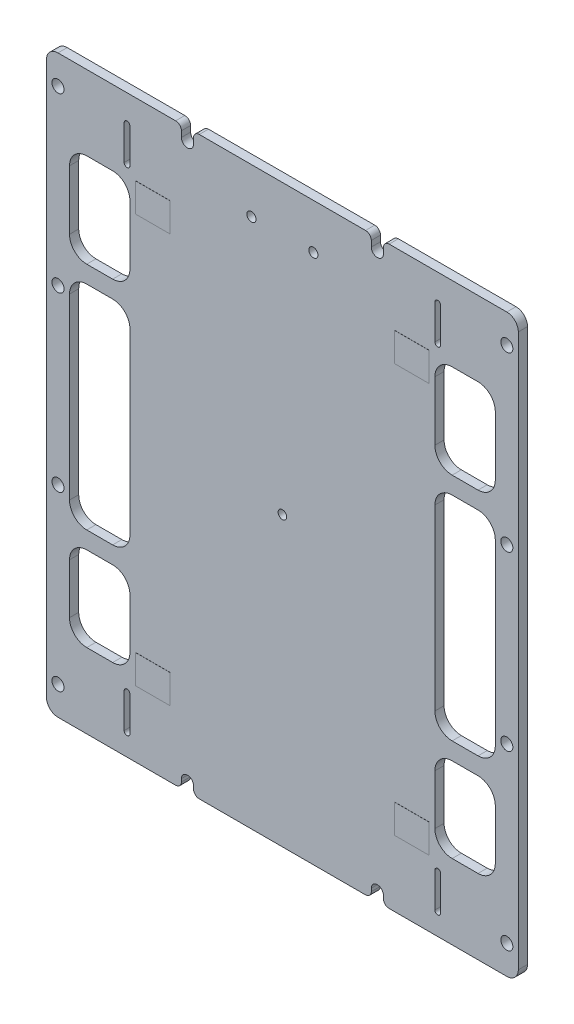
SolidWorks part; units mm, degrees
material "FR4_stuffedProtoboard"
ref_plane "Front Plane" through (0, 0, 0) normal (0, 0, 1) x (1, 0, 0)
ref_plane "Top Plane" through (0, 0, 0) normal (0, 1, 0) x (1, 0, 0)
ref_plane "Right Plane" through (0, 0, 0) normal (1, 0, 0) x (0, 0, -1)
sketch "Sketch1" plane through (0, 0, 0) normal (0, 0, 1) x (1, 0, 0)
  line L1 (-39, -50) -> (39, -50)
  line L2 (-41, -48) -> (-41, 48)
  line L3 (-39, 50) -> (39, 50)
  line L4 (41, -48) -> (41, 48)
  line L5 (-41, -50) -> (41, 50) construction
  line L6 (-41, 50) -> (41, -50) construction
  arc A0 (-39, -50) -> (-41, -48) centre (-39, -48) cw
  arc A1 (39, -50) -> (41, -48) centre (39, -48) ccw
  arc A2 (39, 50) -> (41, 48) centre (39, 48) cw
  arc A3 (-41, 48) -> (-39, 50) centre (-39, 48) cw
  point P0 (0, 0)
  dimension "D3" = 2
  dimension "D1" = 100
  dimension "D2" = 82
extrude "boardOutline" add sketch "Sketch1" along normal blind 1.6
sketch "Sketch2" plane through (0, 0, 1.6) normal (0, 0, 1) x (1, 0, 0)
  line L0 (39, 50) -> (-39, 50) construction
  line L1 (-41, 48) -> (-41, -48) construction
  line L2 (-5.385, 42.15) -> (5.385, 42.15) construction
  line L3 (-37.5, 44.2) -> (-37.5, 4.2) construction
  line L4 (0, 42.15) -> (0, 50) construction
  circle A0 centre (0, 0) radius 0.75
  circle A1 centre (-37.5, 44.2) radius 1.05 construction
  circle A2 centre (37.5, 44.2) radius 1.05 construction
  circle A3 centre (37.5, 4.2) radius 1.05 construction
  circle A4 centre (37.5, -35.8) radius 1.05 construction
  circle A5 centre (-37.5, 4.2) radius 1.05 construction
  circle A6 centre (-37.5, -35.8) radius 1.05 construction
  circle A7 centre (-5.385, 42.15) radius 0.8
  circle A8 centre (5.385, 42.15) radius 0.8
  point P27 (0, 0)
  dimension "D1" = 1.5
  dimension "D2" = 2.1
  dimension "D9" = 10.77
  dimension "D7" = 1.6
  dimension "D11" = 7.85
  dimension "D3" = 5.8
  dimension "D4" = 3.5
  dimension "D8" = 40
  dimension "D10" = 37.5
  dimension "D5" = 2
  dimension "D6" = 3
extrude "componentHoles" cut sketch "Sketch2" against normal through all
sketch "Sketch4" plane through (0, 0, 1.6) normal (0, 0, 1) x (1, 0, 0)
  line L0 (-27, 39.25) -> (-27, 45.25) construction
  line L1 (-27.5, 39.25) -> (-27.5, 45.25)
  line L2 (-26.5, 39.25) -> (-26.5, 45.25)
  line L3 (39, 50) -> (-39, 50) construction
  line L4 (-41, 48) -> (-41, -48) construction
  line L5 (27, 39.25) -> (27, 45.25) construction
  line L6 (26.5, 39.25) -> (26.5, 45.25)
  line L7 (27.5, 39.25) -> (27.5, 45.25)
  line L8 (27, -46.25) -> (27, -40.25) construction
  line L9 (26.5, -46.25) -> (26.5, -40.25)
  line L10 (27.5, -46.25) -> (27.5, -40.25)
  line L11 (-27, -46.25) -> (-27, -40.25) construction
  line L12 (-27.5, -46.25) -> (-27.5, -40.25)
  line L13 (-26.5, -46.25) -> (-26.5, -40.25)
  line L14 (-27, 39.25) -> (27, 39.25) construction
  line L15 (0, 39.25) -> (0, 50) construction
  arc A0 (-27.5, 39.25) -> (-26.5, 39.25) centre (-27, 39.25) ccw
  arc A1 (-26.5, 45.25) -> (-27.5, 45.25) centre (-27, 45.25) ccw
  arc A2 (26.5, 39.25) -> (27.5, 39.25) centre (27, 39.25) ccw
  arc A3 (27.5, 45.25) -> (26.5, 45.25) centre (27, 45.25) ccw
  arc A4 (26.5, -46.25) -> (27.5, -46.25) centre (27, -46.25) ccw
  arc A5 (27.5, -40.25) -> (26.5, -40.25) centre (27, -40.25) ccw
  arc A6 (-27.5, -46.25) -> (-26.5, -46.25) centre (-27, -46.25) ccw
  arc A7 (-26.5, -40.25) -> (-27.5, -40.25) centre (-27, -40.25) ccw
  point P2 (-27, 42.25)
  point P16 (27, 42.25)
  point P23 (27, -43.25)
  point P30 (-27, -43.25)
  dimension "D1" = 4.75
  dimension "D2" = 13.5
  dimension "D3" = 1
  dimension "D4" = 6
  dimension "D7" = 54
  dimension "D9" = 79.5
  dimension "D5" = 2
  dimension "D6" = 2
extrude "solarCellContactHoles" cut sketch "Sketch4" against normal blind 1.6
sketch "Sketch3" plane through (0, 0, 1.6) normal (0, 0, 1) x (1, 0, 0)
  line L1 (-34, 37) -> (-29.5, 37)
  line L2 (-37, 34) -> (-37, 23.7)
  line L3 (-34, 20.7) -> (-29.5, 20.7)
  line L4 (-26.5, 34) -> (-26.5, 23.7)
  line L5 (-41, 48) -> (-41, -48) construction
  line L6 (-29.5, -22.3) -> (-34, -22.3)
  line L9 (0, 50) -> (0, -50) construction
  line L10 (39, 50) -> (-39, 50) construction
  line L11 (-39, -50) -> (39, -50) construction
  line L12 (-26.5, -25.3) -> (-26.5, -34)
  line L13 (-29.5, -37) -> (-34, -37)
  line L14 (-37, -25.3) -> (-37, -34)
  line L19 (-29.5, -19.3) -> (-34, -19.3)
  line L25 (-26.5, -16.3) -> (-26.5, 14.7)
  line L26 (-29.5, 17.7) -> (-34, 17.7)
  line L27 (-37, -16.3) -> (-37, 14.7)
  arc A0 (-37, 23.7) -> (-34, 20.7) centre (-34, 23.7) ccw
  arc A1 (-29.5, 20.7) -> (-26.5, 23.7) centre (-29.5, 23.7) ccw
  arc A2 (-29.5, 37) -> (-26.5, 34) centre (-29.5, 34) cw
  arc A3 (-34, 37) -> (-37, 34) centre (-34, 34) ccw
  arc A4 (-29.5, -19.3) -> (-26.5, -16.3) centre (-29.5, -16.3) ccw
  arc A5 (-26.5, -34) -> (-29.5, -37) centre (-29.5, -34) cw
  arc A6 (-34, -37) -> (-37, -34) centre (-34, -34) cw
  arc A7 (-34, -22.3) -> (-37, -25.3) centre (-34, -25.3) ccw
  arc A8 (-29.5, -22.3) -> (-26.5, -25.3) centre (-29.5, -25.3) cw
  arc A17 (-34, -19.3) -> (-37, -16.3) centre (-34, -16.3) cw
  arc A18 (-34, 17.7) -> (-37, 14.7) centre (-34, 14.7) ccw
  arc A19 (-26.5, 14.7) -> (-29.5, 17.7) centre (-29.5, 14.7) ccw
  point P12 (-26.5, 20.7)
  point P15 (-26.5, 37)
  point P18 (-37, 37)
  dimension "D5" = 3
  dimension "D10" = 13
  dimension "D7" = 3
  dimension "D11" = 3
  dimension "D1" = 10.5
  dimension "D2" = 29.3
  dimension "D3" = 13
  dimension "D4" = 4
  dimension "D8" = 3
  dimension "D9" = 3
  dimension "D6" = 37
extrude "windows_1side" cut sketch "Sketch3" against normal through all
sketch "Sketch5" plane through (0, 0, 1.6) normal (0, 0, 1) x (1, 0, 0)
  line L0 (-41, 48) -> (-41, -48) construction
  line L1 (-25.5, 37.5) -> (-19.5, 37.5)
  line L2 (-25.5, 37.5) -> (-25.5, 32.5)
  line L3 (-25.5, 32.5) -> (-19.5, 32.5)
  line L4 (-19.5, 37.5) -> (-19.5, 32.5)
  line L5 (0, 37.5) -> (0, 50) construction
  line L6 (19.5, 37.5) -> (19.5, 32.5)
  line L7 (25.5, 37.5) -> (25.5, 32.5)
  line L8 (19.5, 32.5) -> (25.5, 32.5)
  line L9 (19.5, 37.5) -> (25.5, 37.5)
  line L10 (19.5, -33.5) -> (19.5, -38.5)
  line L11 (25.5, -33.5) -> (25.5, -38.5)
  line L12 (19.5, -38.5) -> (25.5, -38.5)
  line L13 (19.5, -33.5) -> (25.5, -33.5)
  line L14 (-25.5, -33.5) -> (-25.5, -38.5)
  line L15 (-19.5, -33.5) -> (-19.5, -38.5)
  line L16 (-25.5, -38.5) -> (-19.5, -38.5)
  line L17 (-25.5, -33.5) -> (-19.5, -33.5)
  line L18 (-19.5, 37.5) -> (19.5, 37.5) construction
  line L19 (-25.5, 37.5) -> (-25.5, -33.5) construction
  line L20 (39, 50) -> (-39, 50) construction
  arc A0 (-27.5, 39.25) -> (-26.5, 39.25) centre (-27, 39.25) ccw construction
  point P9 (0, 0)
  dimension "D1" = 5
  dimension "D2" = 6
  dimension "D3" = 15.5
  dimension "D4" = 1.75
  dimension "D7" = 45
  dimension "D8" = 71
  dimension "D5" = 2
  dimension "D6" = 2
extrude "contactPads" add sketch "Sketch5" along normal blind 0.02
hole_wizard "M2 Clearance Hole1" positions "Sketch6" profile "Sketch7" hole size "M2" standard "ANSI Metric" end condition through all
sketch "Sketch6" plane through (0, 0, 0) normal (0, 0, -1) x (-1, 0, 0)
  line L5 (39, -50) -> (39, -45) construction
  line L6 (39, -50) -> (-39, -50) construction
  line L7 (39, -45) -> (39, -15) construction
  line L8 (39, -15) -> (39, 15) construction
  line L9 (39, 15) -> (39, 45) construction
  line L10 (39, 45) -> (39, 50) construction
  line L11 (-39, 50) -> (39, 50) construction
  line L15 (37, -27.0602) -> (41, -27.0602) construction
  line L16 (37, -25.3) -> (37, -34) construction
  line L17 (41, 48) -> (41, -48) construction
  point P0 (39, 45)
  point P27 (39, -15)
  point P36 (39, -45)
  point P38 (39, 15)
  point P73 (39, -27.0602)
  dimension "D2" = 5
sketch "Sketch7" plane through (-39, 45, 0) normal (1, 0, 0) x (0, 1, 0)
  line L0 (0, 0) -> (0, 1.62)
  line L1 (0, 1.62) -> (1.05, 1.62)
  line L2 (1.05, 1.62) -> (1.05, 0)
  line L5 (1.05, 0) -> (0, 0)
  line L11 (0, -6.35) -> (0, 107.95) construction
  dimension "Thru Hole Dia." = 2.1
  dimension "Thru Hole Depth" = 1.62
sketch "Sketch10" plane through (0, 0, 0) normal (0, 0, -1) x (-1, 0, 0)
  line L0 (16.5, 48) -> (16.5, 55.0732) construction
  line L1 (15.45, 48) -> (15.45, 55.0732)
  line L2 (17.55, 48) -> (17.55, 55.0732)
  line L3 (16.5, -48.5) -> (16.5, -55.5732) construction
  line L4 (17.55, -48.5) -> (17.55, -55.5732)
  line L5 (15.45, -48.5) -> (15.45, -55.5732)
  line L6 (41, 48) -> (41, -48) construction
  line L8 (39, -50) -> (-39, -50) construction
  line L9 (-39, 50) -> (39, 50) construction
  arc A0 (15.45, 48) -> (17.55, 48) centre (16.5, 48) ccw
  arc A1 (17.55, 55.0732) -> (15.45, 55.0732) centre (16.5, 55.0732) ccw
  arc A2 (17.55, -48.5) -> (15.45, -48.5) centre (16.5, -48.5) ccw
  arc A3 (15.45, -55.5732) -> (17.55, -55.5732) centre (16.5, -55.5732) ccw
  point P2 (16.5, 51.5366)
  point P7 (16.5, -52.0366)
  dimension "D1" = 1.05
  dimension "D2" = 24.5
  dimension "D3" = 2
  dimension "D4" = 1.5
extrude "Cut-Extrude1" cut sketch "Sketch10" against normal through all both and the other way through all
fillet "Fillet3" radius 1 4 edges at (-17.55, 50, 0.8) (-15.45, 50, 0.8) (-15.45, -50, 0.8) (-17.55, -50, 0.8)
mirror "Mirror1" about plane through (0, 0, 0) normal (1, 0, 0) of "Cut-Extrude1", "Fillet3", "windows_1side", "M2 Clearance Hole1"
sketch "thermalContact" plane through (0, 0, 1.6) normal (0, 0, 1) x (1, 0, 0)
  line L0 (-37, 43) -> (-37, 23.7) construction
  line L1 (-34, 20.7) -> (-21, 20.7) construction
  line L2 (-18, 23.7) -> (-18, 43) construction
  line L3 (-21, 46) -> (-34, 46) construction
  line L4 (-41, 48) -> (-41, -162)
  line L5 (39, 50) -> (-39, 50)
  line L6 (41, -162) -> (41, 48)
  line L7 (-39, -164) -> (39, -164)
  line L8 (-41, 48) -> (-41, -162)
  line L9 (39, 50) -> (-39, 50)
  line L10 (41, -162) -> (41, 48)
  line L11 (-39, -164) -> (39, -164)
  line L12 (-37, 43) -> (-37, 23.7)
  line L13 (-34, 20.7) -> (-21, 20.7)
  line L14 (-18, 23.7) -> (-18, 43)
  line L15 (-21, 46) -> (-34, 46)
  line L16 (18, 43) -> (18, 23.7) construction
  line L17 (21, 20.7) -> (34, 20.7) construction
  line L18 (37, 23.7) -> (37, 43) construction
  line L19 (34, 46) -> (21, 46) construction
  line L20 (18, 43) -> (18, 23.7)
  line L21 (21, 20.7) -> (34, 20.7)
  line L22 (37, 23.7) -> (37, 43)
  line L23 (34, 46) -> (21, 46)
  line L24 (-12, -47) -> (12, -47) construction
  line L25 (15, -44) -> (15, -25.3) construction
  line L26 (12, -22.3) -> (-12, -22.3) construction
  line L27 (-15, -25.3) -> (-15, -44) construction
  line L28 (-12, -47) -> (12, -47)
  line L29 (15, -44) -> (15, -25.3)
  line L30 (12, -22.3) -> (-12, -22.3)
  line L31 (-15, -25.3) -> (-15, -44)
  line L32 (-37, -25.3) -> (-37, -44) construction
  line L33 (-34, -47) -> (-21, -47) construction
  line L34 (-18, -44) -> (-18, -25.3) construction
  line L35 (-21, -22.3) -> (-34, -22.3) construction
  line L36 (-37, -25.3) -> (-37, -44)
  line L37 (-34, -47) -> (-21, -47)
  line L38 (-18, -44) -> (-18, -25.3)
  line L39 (-21, -22.3) -> (-34, -22.3)
  line L40 (18, -25.3) -> (18, -44) construction
  line L41 (21, -47) -> (34, -47) construction
  line L42 (37, -44) -> (37, -25.3) construction
  line L43 (34, -22.3) -> (21, -22.3) construction
  line L44 (18, -25.3) -> (18, -44)
  line L45 (21, -47) -> (34, -47)
  line L46 (37, -44) -> (37, -25.3)
  line L47 (34, -22.3) -> (21, -22.3)
  line L48 (-12, -19.3) -> (12, -19.3) construction
  line L49 (15, -16.3) -> (15, 14.7) construction
  line L50 (12, 17.7) -> (-12, 17.7) construction
  line L51 (-15, 14.7) -> (-15, -16.3) construction
  line L52 (-12, -19.3) -> (12, -19.3)
  line L53 (15, -16.3) -> (15, 14.7)
  line L54 (12, 17.7) -> (-12, 17.7)
  line L55 (-15, 14.7) -> (-15, -16.3)
  line L56 (-21, 17.7) -> (-34, 17.7) construction
  line L57 (-37, 14.7) -> (-37, -16.3) construction
  line L58 (-34, -19.3) -> (-21, -19.3) construction
  line L59 (-18, -16.3) -> (-18, 14.7) construction
  line L60 (-21, 17.7) -> (-34, 17.7)
  line L61 (-37, 14.7) -> (-37, -16.3)
  line L62 (-34, -19.3) -> (-21, -19.3)
  line L63 (-18, -16.3) -> (-18, 14.7)
  line L64 (21, -19.3) -> (34, -19.3) construction
  line L65 (37, -16.3) -> (37, 14.7) construction
  line L66 (34, 17.7) -> (21, 17.7) construction
  line L67 (18, 14.7) -> (18, -16.3) construction
  line L68 (21, -19.3) -> (34, -19.3)
  line L69 (37, -16.3) -> (37, 14.7)
  line L70 (34, 17.7) -> (21, 17.7)
  line L71 (18, 14.7) -> (18, -16.3)
  line L72 (-12, 20.7) -> (12, 20.7) construction
  line L73 (15, 23.7) -> (15, 43) construction
  line L74 (12, 46) -> (-12, 46) construction
  line L75 (-15, 43) -> (-15, 23.7) construction
  line L76 (-12, 20.7) -> (12, 20.7)
  line L77 (15, 23.7) -> (15, 43)
  line L78 (12, 46) -> (-12, 46)
  line L79 (-15, 43) -> (-15, 23.7)
  line L80 (-21, -50) -> (-34, -50) construction
  line L81 (-37, -53) -> (-37, -61) construction
  line L82 (-34, -64) -> (-21, -64) construction
  line L83 (-18, -61) -> (-18, -53) construction
  line L84 (-21, -50) -> (-34, -50)
  line L85 (-37, -53) -> (-37, -61)
  line L86 (-34, -64) -> (-21, -64)
  line L87 (-18, -61) -> (-18, -53)
  line L88 (-15, -53) -> (-15, -61) construction
  line L89 (-12, -64) -> (12, -64) construction
  line L90 (15, -61) -> (15, -53) construction
  line L91 (12, -50) -> (-12, -50) construction
  line L92 (-15, -53) -> (-15, -61)
  line L93 (-12, -64) -> (12, -64)
  line L94 (15, -61) -> (15, -53)
  line L95 (12, -50) -> (-12, -50)
  line L96 (18, -53) -> (18, -61) construction
  line L97 (21, -64) -> (34, -64) construction
  line L98 (37, -61) -> (37, -53) construction
  line L99 (34, -50) -> (21, -50) construction
  line L100 (18, -53) -> (18, -61)
  line L101 (21, -64) -> (34, -64)
  line L102 (37, -61) -> (37, -53)
  line L103 (34, -50) -> (21, -50)
  arc A0 (-34, 46) -> (-37, 43) centre (-34, 43) ccw construction
  arc A1 (-37, 23.7) -> (-34, 20.7) centre (-34, 23.7) ccw construction
  arc A2 (-21, 20.7) -> (-18, 23.7) centre (-21, 23.7) ccw construction
  arc A3 (-18, 43) -> (-21, 46) centre (-21, 43) ccw construction
  arc A4 (-39, 50) -> (-41, 48) centre (-39, 48) ccw
  arc A5 (41, 48) -> (39, 50) centre (39, 48) ccw
  arc A6 (39, -164) -> (41, -162) centre (39, -162) ccw
  arc A7 (-41, -162) -> (-39, -164) centre (-39, -162) ccw
  arc A8 (-39, 50) -> (-41, 48) centre (-39, 48) ccw
  arc A9 (41, 48) -> (39, 50) centre (39, 48) ccw
  arc A10 (39, -164) -> (41, -162) centre (39, -162) ccw
  arc A11 (-41, -162) -> (-39, -164) centre (-39, -162) ccw
  arc A12 (-34, 46) -> (-37, 43) centre (-34, 43) ccw
  arc A13 (-37, 23.7) -> (-34, 20.7) centre (-34, 23.7) ccw
  arc A14 (-21, 20.7) -> (-18, 23.7) centre (-21, 23.7) ccw
  arc A15 (-18, 43) -> (-21, 46) centre (-21, 43) ccw
  arc A16 (21, 46) -> (18, 43) centre (21, 43) ccw construction
  arc A17 (18, 23.7) -> (21, 20.7) centre (21, 23.7) ccw construction
  arc A18 (34, 20.7) -> (37, 23.7) centre (34, 23.7) ccw construction
  arc A19 (37, 43) -> (34, 46) centre (34, 43) ccw construction
  arc A20 (21, 46) -> (18, 43) centre (21, 43) ccw
  arc A21 (18, 23.7) -> (21, 20.7) centre (21, 23.7) ccw
  arc A22 (34, 20.7) -> (37, 23.7) centre (34, 23.7) ccw
  arc A23 (37, 43) -> (34, 46) centre (34, 43) ccw
  arc A24 (-15, -44) -> (-12, -47) centre (-12, -44) ccw construction
  arc A25 (12, -47) -> (15, -44) centre (12, -44) ccw construction
  arc A26 (15, -25.3) -> (12, -22.3) centre (12, -25.3) ccw construction
  arc A27 (-12, -22.3) -> (-15, -25.3) centre (-12, -25.3) ccw construction
  arc A28 (-15, -44) -> (-12, -47) centre (-12, -44) ccw
  arc A29 (12, -47) -> (15, -44) centre (12, -44) ccw
  arc A30 (15, -25.3) -> (12, -22.3) centre (12, -25.3) ccw
  arc A31 (-12, -22.3) -> (-15, -25.3) centre (-12, -25.3) ccw
  arc A32 (-34, -22.3) -> (-37, -25.3) centre (-34, -25.3) ccw construction
  arc A33 (-37, -44) -> (-34, -47) centre (-34, -44) ccw construction
  arc A34 (-21, -47) -> (-18, -44) centre (-21, -44) ccw construction
  arc A35 (-18, -25.3) -> (-21, -22.3) centre (-21, -25.3) ccw construction
  arc A36 (-34, -22.3) -> (-37, -25.3) centre (-34, -25.3) ccw
  arc A37 (-37, -44) -> (-34, -47) centre (-34, -44) ccw
  arc A38 (-21, -47) -> (-18, -44) centre (-21, -44) ccw
  arc A39 (-18, -25.3) -> (-21, -22.3) centre (-21, -25.3) ccw
  arc A40 (21, -22.3) -> (18, -25.3) centre (21, -25.3) ccw construction
  arc A41 (18, -44) -> (21, -47) centre (21, -44) ccw construction
  arc A42 (34, -47) -> (37, -44) centre (34, -44) ccw construction
  arc A43 (37, -25.3) -> (34, -22.3) centre (34, -25.3) ccw construction
  arc A44 (21, -22.3) -> (18, -25.3) centre (21, -25.3) ccw
  arc A45 (18, -44) -> (21, -47) centre (21, -44) ccw
  arc A46 (34, -47) -> (37, -44) centre (34, -44) ccw
  arc A47 (37, -25.3) -> (34, -22.3) centre (34, -25.3) ccw
  arc A48 (-15, -16.3) -> (-12, -19.3) centre (-12, -16.3) ccw construction
  arc A49 (12, -19.3) -> (15, -16.3) centre (12, -16.3) ccw construction
  arc A50 (15, 14.7) -> (12, 17.7) centre (12, 14.7) ccw construction
  arc A51 (-12, 17.7) -> (-15, 14.7) centre (-12, 14.7) ccw construction
  arc A52 (-15, -16.3) -> (-12, -19.3) centre (-12, -16.3) ccw
  arc A53 (12, -19.3) -> (15, -16.3) centre (12, -16.3) ccw
  arc A54 (15, 14.7) -> (12, 17.7) centre (12, 14.7) ccw
  arc A55 (-12, 17.7) -> (-15, 14.7) centre (-12, 14.7) ccw
  arc A56 (-18, 14.7) -> (-21, 17.7) centre (-21, 14.7) ccw construction
  arc A57 (-34, 17.7) -> (-37, 14.7) centre (-34, 14.7) ccw construction
  arc A58 (-37, -16.3) -> (-34, -19.3) centre (-34, -16.3) ccw construction
  arc A59 (-21, -19.3) -> (-18, -16.3) centre (-21, -16.3) ccw construction
  arc A60 (-18, 14.7) -> (-21, 17.7) centre (-21, 14.7) ccw
  arc A61 (-34, 17.7) -> (-37, 14.7) centre (-34, 14.7) ccw
  arc A62 (-37, -16.3) -> (-34, -19.3) centre (-34, -16.3) ccw
  arc A63 (-21, -19.3) -> (-18, -16.3) centre (-21, -16.3) ccw
  arc A64 (18, -16.3) -> (21, -19.3) centre (21, -16.3) ccw construction
  arc A65 (34, -19.3) -> (37, -16.3) centre (34, -16.3) ccw construction
  arc A66 (37, 14.7) -> (34, 17.7) centre (34, 14.7) ccw construction
  arc A67 (21, 17.7) -> (18, 14.7) centre (21, 14.7) ccw construction
  arc A68 (18, -16.3) -> (21, -19.3) centre (21, -16.3) ccw
  arc A69 (34, -19.3) -> (37, -16.3) centre (34, -16.3) ccw
  arc A70 (37, 14.7) -> (34, 17.7) centre (34, 14.7) ccw
  arc A71 (21, 17.7) -> (18, 14.7) centre (21, 14.7) ccw
  arc A72 (-15, 23.7) -> (-12, 20.7) centre (-12, 23.7) ccw construction
  arc A73 (12, 20.7) -> (15, 23.7) centre (12, 23.7) ccw construction
  arc A74 (15, 43) -> (12, 46) centre (12, 43) ccw construction
  arc A75 (-12, 46) -> (-15, 43) centre (-12, 43) ccw construction
  arc A76 (-15, 23.7) -> (-12, 20.7) centre (-12, 23.7) ccw
  arc A77 (12, 20.7) -> (15, 23.7) centre (12, 23.7) ccw
  arc A78 (15, 43) -> (12, 46) centre (12, 43) ccw
  arc A79 (-12, 46) -> (-15, 43) centre (-12, 43) ccw
  arc A80 (-34, -50) -> (-37, -53) centre (-34, -53) ccw construction
  arc A81 (-37, -61) -> (-34, -64) centre (-34, -61) ccw construction
  arc A82 (-21, -64) -> (-18, -61) centre (-21, -61) ccw construction
  arc A83 (-18, -53) -> (-21, -50) centre (-21, -53) ccw construction
  arc A84 (-34, -50) -> (-37, -53) centre (-34, -53) ccw
  arc A85 (-37, -61) -> (-34, -64) centre (-34, -61) ccw
  arc A86 (-21, -64) -> (-18, -61) centre (-21, -61) ccw
  arc A87 (-18, -53) -> (-21, -50) centre (-21, -53) ccw
  arc A88 (-15, -61) -> (-12, -64) centre (-12, -61) ccw construction
  arc A89 (12, -64) -> (15, -61) centre (12, -61) ccw construction
  arc A90 (15, -53) -> (12, -50) centre (12, -53) ccw construction
  arc A91 (-12, -50) -> (-15, -53) centre (-12, -53) ccw construction
  arc A92 (-15, -61) -> (-12, -64) centre (-12, -61) ccw
  arc A93 (12, -64) -> (15, -61) centre (12, -61) ccw
  arc A94 (15, -53) -> (12, -50) centre (12, -53) ccw
  arc A95 (-12, -50) -> (-15, -53) centre (-12, -53) ccw
  arc A96 (21, -50) -> (18, -53) centre (21, -53) ccw construction
  arc A97 (18, -61) -> (21, -64) centre (21, -61) ccw construction
  arc A98 (34, -64) -> (37, -61) centre (34, -61) ccw construction
  arc A99 (37, -53) -> (34, -50) centre (34, -53) ccw construction
  arc A100 (18, -61) -> (21, -64) centre (21, -61) ccw
  arc A101 (34, -64) -> (37, -61) centre (34, -61) ccw
  arc A102 (37, -53) -> (34, -50) centre (34, -53) ccw
  arc A103 (21, -50) -> (18, -53) centre (21, -53) ccw
  dimension "D1" = 0
